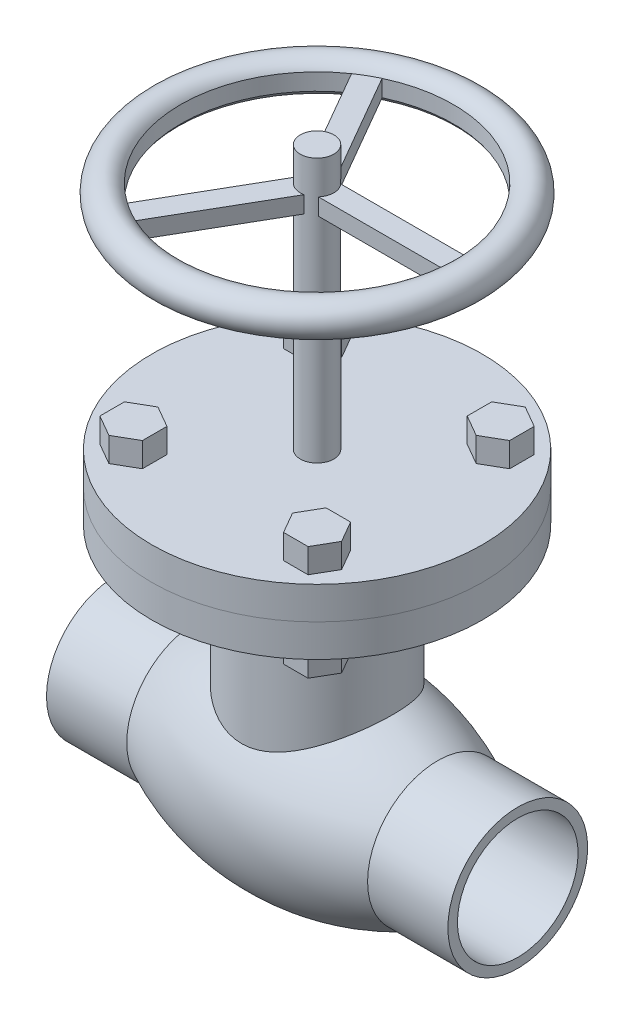
SolidWorks part; units mm, degrees
ref_plane "Front Plane" through (0, 0, 0) normal (0, 0, 1) x (1, 0, 0)
ref_plane "Top Plane" through (0, 0, 0) normal (0, 1, 0) x (1, 0, 0)
ref_plane "Right Plane" through (0, 0, 0) normal (1, 0, 0) x (0, 0, -1)
sketch "Flow Extrude Sketch" plane through (0, 0, 0) normal (0, 0, 1) x (1, 0, 0)
  line L0 (-109.6823, 0) -> (110.5039, 0) construction
  line L1 (0, 0) -> (0, 85.3189) construction
  line L2 (64.77, 37.592) -> (107.95, 37.592)
  line L3 (-107.95, 37.592) -> (-64.77, 37.592)
  line L4 (-107.95, 37.592) -> (-107.95, 0)
  line L5 (-107.95, 0) -> (107.95, 0)
  line L6 (107.95, 37.592) -> (107.95, 0)
  arc A1 (-64.77, 37.592) -> (64.77, 37.592) centre (0, -94.3858) cw
  point P13 (0, 52.6288)
  dimension "A" = 75.184
  dimension "B" = 215.9
  dimension "A*1.4" = 105.2576
  dimension "B*.6" = 129.54
revolve "Flow Extrude" add sketch "Flow Extrude Sketch" angle 360 about L0
sketch "Body Extrude Sketch" plane through (0, 0, 0) normal (0, 1, 0) x (1, 0, 0)
  line L1 (0, -96.6135) -> (0, 96.6135) construction
  circle A0 centre (0, 0) radius 40.6108
  dimension "(A+2*t)*0.95" = 81.2216
extrude "Body Extrude" add sketch "Body Extrude Sketch" along normal blind 115.189
sketch "Flange Bottom Sketch" plane through (0, 115.189, 0) normal (0, 1, 0) x (-1, 0, 0)
  circle A0 centre (0, 0) radius 88.9
  dimension "O" = 177.8
extrude "Flange Bottom" add sketch "Flange Bottom Sketch" along normal blind 17.526
sketch "Flange Top Sketch" plane through (0, 132.715, 0) normal (0, 1, 0) x (-1, 0, 0)
  circle A1 centre (0, 0) radius 88.9
  circle A2 centre (0, 0) radius 88.9
  dimension "D1" = 0
extrude "Flange Top" add sketch "Flange Top Sketch" along normal blind 17.526
ref_plane "Driver Plane" through (0, 269.748, 0) normal (0, 1, 0) x (-1, 0, 0)
sketch "Driver Path" plane through (0, 269.748, 0) normal (0, 1, 0) x (-1, 0, 0)
  circle A0 centre (0, 0) radius 90.17
  dimension "D" = 180.34
sketch "Driver Profile" plane through (0, 0, 0) normal (0, 0, 1) x (1, 0, 0)
  line L0 (90.17, 269.748) -> (-90.17, 269.748) construction
  line L1 (-73.344, 274.2565) -> (0, 274.2565)
  line L2 (90.17, 269.748) -> (-90.17, 269.748) construction
  line L3 (-73.344, 265.2395) -> (0, 265.2395)
  line L4 (0, 274.2565) -> (0, 265.2395)
  arc A0 (-73.344, 274.2565) -> (-73.344, 265.2395) centre (-81.153, 269.748) ccw
  dimension "D1" = 9.017
  dimension "D/20" = 9.017
sweep "Driver Sweep" add profiles "Driver Profile" path "Driver Path"
sketch "Centre Support Sketch" plane through (0, 274.2565, 0) normal (0, 1, 0) x (-1, 0, 0)
  circle A0 centre (0, 0) radius 9.017
  dimension "D/10" = 18.034
extrude "Centre Support" add sketch "Centre Support Sketch" against normal up to surface (124.0155 mm away) and the other way blind 18.034 up to face at (0, 150.241, 88.9)
sketch "Driver Cut Sketch" plane through (0, 274.2565, 0) normal (0, 1, 0) x (-1, 0, 0)
  line L0 (0, 0) -> (0, 113.8697) construction
  line L1 (0, 0) -> (-104.7757, 0) construction
  line L2 (31.3427, 66.3098) -> (-1.8455, 8.8261)
  line L3 (-73.0973, -6.0113) -> (-6.7209, -6.0113)
  line L4 (41.7546, 60.2984) -> (8.5664, 2.8148)
  line L5 (-73.0973, 6.0113) -> (-6.7209, 6.0113)
  line L6 (41.7546, -60.2984) -> (8.5664, -2.8148)
  line L7 (31.3427, -66.3098) -> (-1.8455, -8.8261)
  circle A0 centre (0, 0) radius 73.344 construction
  arc A1 (31.3427, 66.3098) -> (-73.0973, 6.0113) centre (0, 0) ccw
  circle A2 centre (0, 0) radius 9.017 construction
  arc A3 (-6.7209, -6.0113) -> (-1.8455, -8.8261) centre (0, 0) ccw
  arc A4 (-1.8455, 8.8261) -> (-6.7209, 6.0113) centre (0, 0) ccw
  arc A5 (8.5664, -2.8148) -> (8.5664, 2.8148) centre (0, 0) ccw
  arc A6 (41.7546, -60.2984) -> (41.7546, 60.2984) centre (0, 0) ccw
  arc A7 (-73.0973, -6.0113) -> (31.3427, -66.3098) centre (0, 0) ccw
  dimension "D/30" = 6.0113
extrude "Driver Cut" cut sketch "Driver Cut Sketch" against normal up to surface (9.017 mm away) up to face at (0, 265.2395, 9.017)
sketch "ID Sketch" plane through (107.95, 0, 0) normal (-1, 0, 0) x (0, 0, 1)
  circle A0 centre (0, 0) radius 32.4358
  dimension "A-2*t" = 64.8716
extrude "ID Cut" cut sketch "ID Sketch" along normal through all
ref_plane "Bolt Plane" through (0, 163.3855, 0) normal (0, 1, 0) x (-1, 0, 0)
sketch "Bolt Sketch" plane through (0, 163.3855, 0) normal (0, 1, 0) x (-1, 0, 0)
  line L0 (0, 0) -> (-97.4469, -97.4469) construction
  line L1 (0, 0) -> (-142.2485, 0) construction
  line L2 (-49.3914, -36.1932) -> (-60.8214, -42.7923)
  line L3 (-60.8214, -42.7923) -> (-60.8214, -55.9905)
  line L4 (-60.8214, -55.9905) -> (-49.3914, -62.5896)
  line L5 (-49.3914, -62.5896) -> (-37.9614, -55.9905)
  line L6 (-37.9614, -55.9905) -> (-37.9614, -42.7923)
  line L7 (-37.9614, -42.7923) -> (-49.3914, -36.1932)
  circle A0 centre (0, 0) radius 69.85 construction
  circle A2 centre (-49.3914, -49.3914) radius 11.43 construction
  dimension "BC" = 139.7
  dimension "DH*1.2" = 22.86
  dimension "Angle" = 45
extrude "Bolt" add sketch "Bolt Sketch" against normal blind 61.341
pattern_circular "Bolt Pattern" count 4 every 90 about axis through (0, 132.715, 0) along (0, -1, 0) of "Bolt"
sketch "Sketch1" plane through (0, 0, 0) normal (0, 0, 1) x (1, 0, 0)
  line L1 (88.9, 132.715) -> (-88.9, 132.715)
  line L2 (88.9, 132.715) -> (-88.9, 132.715)
  dimension "D1" = 0
split line "Split Line1"
sketch "CPointSketch" plane through (0, 0, 0) normal (0, 0, 1) x (1, 0, 0)
  line L2 (107.95, -37.592) -> (107.95, 37.592) construction
  line L3 (-107.95, 37.592) -> (-107.95, -37.592) construction
  point P0 (-107.95, 0)
  point P1 (107.95, 0)
  point P4 (0, 0)
other "CPoint1" parameters "Diameter"=63.5, "StubLength"=0
ref_axis "Axis1" through (117.95, 0, 0) along (-1, 0, 0)
other "CPoint2" parameters "Diameter"=63.5, "StubLength"=0
ref_axis "Axis2" through (-117.95, 0, 0) along (1, 0, 0)
other "RPoint1"
equation "\"D1@Driver Profile\" = \"D/20@Driver Profile\""
equation "\"D2@Centre Support\" = \"D/10@Centre Support Sketch\""
